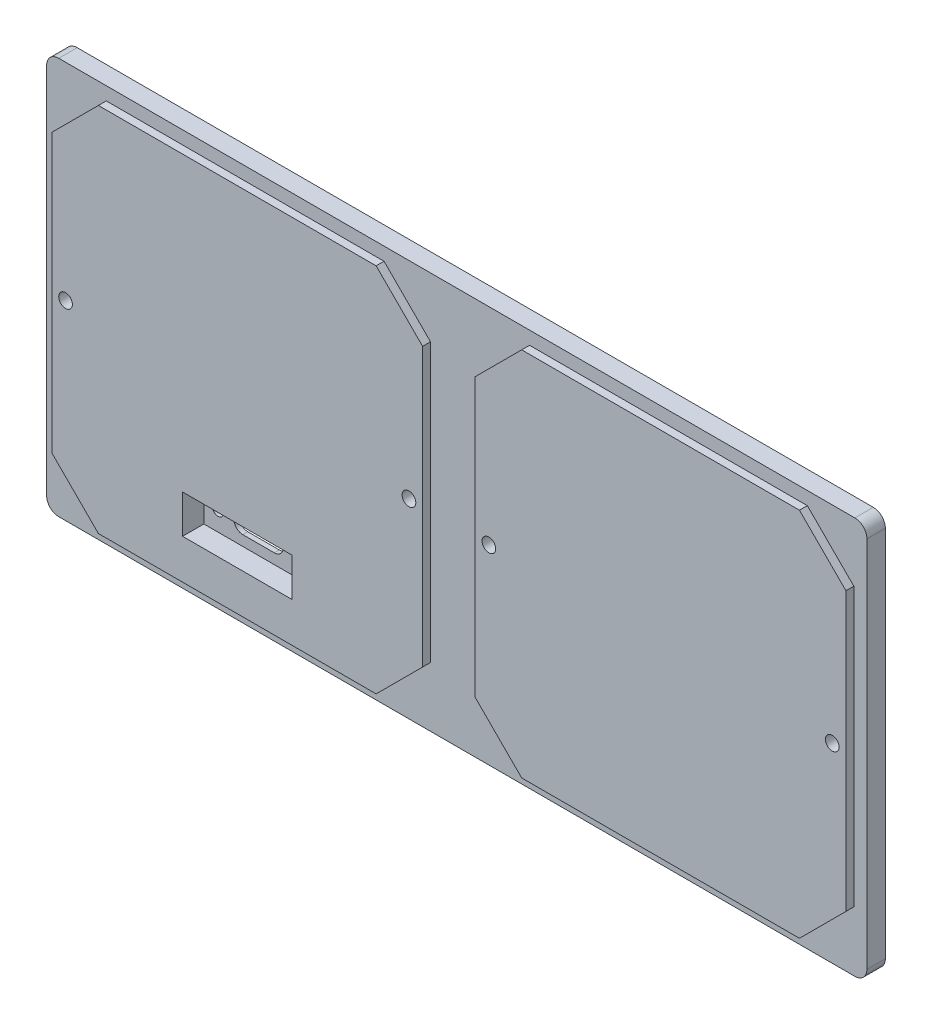
SolidWorks part; units mm, degrees
ref_plane "前视基准面" through (0, 0, 0) normal (0, 0, 1) x (1, 0, 0)
ref_plane "上视基准面" through (0, 0, 0) normal (0, 1, 0) x (1, 0, 0)
ref_plane "右视基准面" through (0, 0, 0) normal (1, 0, 0) x (0, 0, -1)
sketch "草图1" plane through (0, 0, 0) normal (0, 0, 1) x (1, 0, 0)
  line L0 (-72.9, 0) -> (-7.6, 0) construction
  line L1 (-78, -37.75) -> (78, -37.75)
  line L2 (-78, -37.75) -> (-78, 37.75)
  line L3 (-78, 37.75) -> (78, 37.75)
  line L4 (78, -37.75) -> (78, 37.75)
  line L5 (-78, -37.75) -> (78, 37.75) construction
  line L6 (-78, 37.75) -> (78, -37.75) construction
  line L7 (-78, 42.7368) -> (-2.5, 42.7368) construction
  line L8 (78, 42.6441) -> (2.5, 42.6441) construction
  line L9 (0, 0) -> (0, -21.796) construction
  circle A0 centre (-72.9, 0) radius 1.3
  circle A1 centre (-7.6, 0) radius 1.3
  circle A2 centre (7.6, 0) radius 1.3
  circle A3 centre (72.9, 0) radius 1.3
  point P0 (0, 0)
  point P11 (-78, 0)
  point P15 (-40.25, 0)
  point P16 (-40.25, 42.7368)
  dimension "D1" = 2.6
  dimension "D2" = 75.5
  dimension "D3" = 5
  dimension "D4" = 65.3
  dimension "D5" = 75.5
extrude "凸台-拉伸1" add sketch "草图1" along normal blind 5
fillet "圆角1" radius 2.3 4 edges at (78, -37.75, 2.5) (-78, -37.75, 2.5) (78, 37.75, 2.5) (-78, 37.75, 2.5)
sketch "草图2" plane through (0, 0, 5) normal (0, 0, 1) x (1, 0, 0)
  line L1 (-75.5, 26.4112) -> (-75.5, -26.4112)
  line L2 (-78, 42.7368) -> (-2.5, 42.7368) construction
  line L3 (-66.6612, 35.25) -> (-75.5, 26.4112)
  line L5 (0, 0) -> (0, 25.0604) construction
  line L6 (66.6612, 35.25) -> (75.5, 26.4112)
  line L12 (-66.6612, 35.25) -> (-13.8388, 35.25)
  line L13 (66.6612, 35.25) -> (13.8388, 35.25)
  line L14 (-13.8388, 35.25) -> (-5, 26.4112)
  line L15 (-5, 26.4112) -> (-5, -26.4112)
  line L16 (-75.7, -37.75) -> (75.7, -37.75)
  line L17 (78, -35.45) -> (78, 35.45)
  line L18 (75.7, 37.75) -> (-75.7, 37.75)
  line L19 (-78, 35.45) -> (-78, -35.45)
  line L20 (-75.7, -37.75) -> (75.7, -37.75)
  line L21 (78, -35.45) -> (78, 35.45)
  line L22 (75.7, 37.75) -> (-75.7, 37.75)
  line L23 (-78, 35.45) -> (-78, -35.45)
  line L24 (-5, -26.4112) -> (-13.8388, -35.25)
  line L25 (-13.8388, -35.25) -> (-66.6612, -35.25)
  line L26 (-66.6612, -35.25) -> (-75.5, -26.4112)
  line L27 (13.8388, 35.25) -> (5, 26.4112)
  line L28 (5, 26.4112) -> (5, -26.4112)
  line L29 (5, -26.4112) -> (13.8388, -35.25)
  line L30 (13.8388, -35.25) -> (66.6612, -35.25)
  line L31 (66.6612, -35.25) -> (75.5, -26.4112)
  line L32 (75.5, 26.4112) -> (75.5, -26.4112)
  arc A4 (75.7, -37.75) -> (78, -35.45) centre (75.7, -35.45) ccw
  arc A5 (78, 35.45) -> (75.7, 37.75) centre (75.7, 35.45) ccw
  arc A6 (-75.7, 37.75) -> (-78, 35.45) centre (-75.7, 35.45) ccw
  arc A7 (-78, -35.45) -> (-75.7, -37.75) centre (-75.7, -35.45) ccw
  arc A8 (75.7, -37.75) -> (78, -35.45) centre (75.7, -35.45) ccw
  arc A9 (78, 35.45) -> (75.7, 37.75) centre (75.7, 35.45) ccw
  arc A10 (-75.7, 37.75) -> (-78, 35.45) centre (-75.7, 35.45) ccw
  arc A11 (-78, -35.45) -> (-75.7, -37.75) centre (-75.7, -35.45) ccw
  point P13 (-40.25, 42.7368)
  point P16 (-40.25, 35.25)
  dimension "D1" = 135
  dimension "D2" = 12.5
  dimension "D3" = 2.5
  dimension "D4" = 2.5
  dimension "D6" = 2.5
  dimension "D5" = 0
extrude "切除-拉伸1" cut sketch "草图2" against normal blind 1.5
sketch "草图5" plane through (0, 0, 0) normal (0, 0, -1) x (-1, 0, 0)
  circle A0 centre (72.9, 0) radius 1.3 construction
  circle A1 centre (7.6, 0) radius 1.3 construction
  circle A2 centre (-7.6, 0) radius 1.3 construction
  circle A3 centre (-72.9, 0) radius 1.3 construction
  circle A4 centre (72.9, 0) radius 1.3
  circle A5 centre (7.6, 0) radius 1.3
  circle A6 centre (-7.6, 0) radius 1.3
  circle A7 centre (-72.9, 0) radius 1.3
  circle A8 centre (72.9, 0) radius 2.55
  circle A9 centre (7.6, 0) radius 2.55
  circle A10 centre (-7.6, 0) radius 2.55
  circle A11 centre (-72.9, 0) radius 2.55
  dimension "D1" = 1.25
extrude "切除-拉伸4" cut sketch "草图5" against normal offset from surface (2.8 mm away) 2.2 up to face at (71.6, 0, 5)
sketch "草图3" plane through (0, 0, 0) normal (0, 0, -1) x (-1, 0, 0)
  line L0 (37.25, -24.05) -> (43.25, -24.05) construction
  line L1 (37.25, -22.35) -> (43.25, -22.35)
  line L2 (37.25, -25.75) -> (43.25, -25.75)
  line L3 (75.7, -37.75) -> (-75.7, -37.75) construction
  line L4 (78, 42.7368) -> (2.5, 42.7368) construction
  line L5 (40.25, -24.05) -> (40.25, -16.0574) construction
  arc A0 (37.25, -22.35) -> (37.25, -25.75) centre (37.25, -24.05) ccw
  arc A1 (43.25, -25.75) -> (43.25, -22.35) centre (43.25, -24.05) ccw
  circle A2 centre (47.95, -24.05) radius 1.05
  circle A3 centre (32.55, -24.05) radius 1.05
  point P2 (40.25, -24.05)
  point P11 (40.25, 42.7368)
  dimension "D2" = 9.4
  dimension "D4" = 2.1
  dimension "D1" = 3.4
  dimension "D3" = 12
  dimension "D5" = 3
extrude "切除-拉伸2" cut sketch "草图3" against normal through all
sketch "草图4" plane through (0, 0, 5) normal (0, 0, 1) x (1, 0, 0)
  line L1 (-50.65, -27.7) -> (-29.85, -27.7)
  line L2 (-50.65, -27.7) -> (-50.65, -20.4)
  line L3 (-50.65, -20.4) -> (-29.85, -20.4)
  line L4 (-29.85, -27.7) -> (-29.85, -20.4)
  line L5 (-50.65, -27.7) -> (-29.85, -20.4) construction
  line L6 (-50.65, -20.4) -> (-29.85, -27.7) construction
  point P0 (-40.25, -24.05)
  point P5 (0, 0)
  dimension "D1" = 7.3
  dimension "D2" = 20.8
extrude "切除-拉伸3" cut sketch "草图4" against normal offset from surface (4.05 mm away) 0.95 up to face at (-31.5, -24.05, 0)
